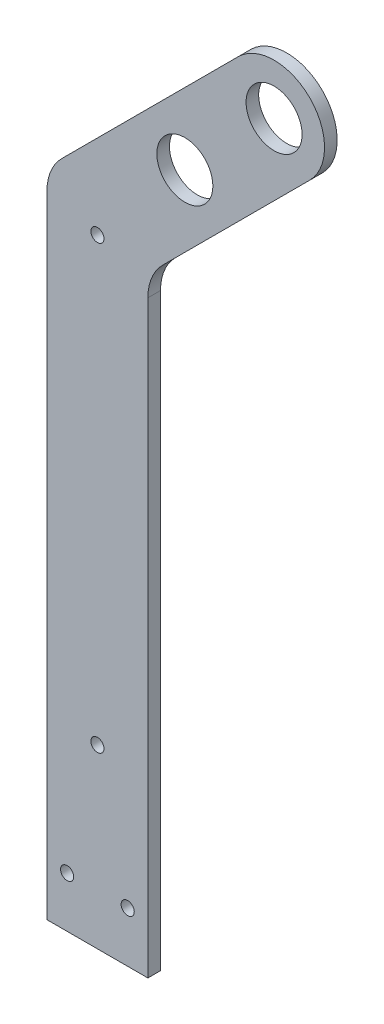
SolidWorks part; units mm, degrees
material "6061 合金"
ref_plane "前视基准面" through (0, 0, 0) normal (0, 0, 1) x (1, 0, 0)
ref_plane "上视基准面" through (0, 0, 0) normal (0, 1, 0) x (1, 0, 0)
ref_plane "右视基准面" through (0, 0, 0) normal (1, 0, 0) x (0, 0, -1)
other "Configuration Table"
sketch "草图1" plane through (0, 0, 0) normal (0, 0, 1) x (1, 0, 0)
  circle A0 centre (0, 0) radius 20
  circle A1 centre (0, 0) radius 11.1
  dimension "D1" = 40
  dimension "D2" = 22.2
extrude "凸台-拉伸1" add sketch "草图1" along normal blind 60 contours A1 | A0 region at (0, 0, 0)
ref_plane "基准面1" through (0, 0, 30) normal (0, 0, 1) x (1, 0, 0)
sketch "草图2" plane through (0, 0, 30) normal (0, 0, 1) x (1, 0, 0)
  line L0 (0, 0) -> (-70, -70) construction
  line L1 (-70, -70) -> (-70, -320) construction
  line L2 (0, -57.3148) -> (0, 49.9409) construction
  line L3 (-56.8582, 0) -> (46.4003, 0) construction
  line L4 (-14.1421, 14.1421) -> (-90, -61.7157)
  line L5 (14.1421, -14.1421) -> (-50, -78.2843)
  line L6 (-90, -61.7157) -> (-90, -320)
  line L7 (-50, -78.2843) -> (-50, -320)
  line L8 (-90, -320) -> (-50, -320)
  circle A2 centre (0, 0) radius 20 construction
  arc A3 (-14.1421, 14.1421) -> (14.1421, -14.1421) centre (0, 0) ccw
  dimension "D1" = 45
  dimension "D2" = 250
  dimension "D3" = 70
  dimension "D4" = 40
  dimension "D5" = 40
extrude "凸台-拉伸2" add sketch "草图2" along normal mid plane 60 contours L7 L8 L6 L4 A3 L5
sketch "草图4" plane through (0, 0, 60) normal (0, 0, 1) x (1, 0, 0)
  line L0 (-90, -61.7157) -> (-90, -320) construction
  line L1 (-90, -290) -> (-50, -290)
  line L2 (-90, -290) -> (-90, -350)
  line L4 (-50, -290) -> (-50, -350)
  line L5 (-50, -78.2843) -> (-50, -320) construction
  line L6 (-90, -320) -> (-50, -320) construction
  arc A0 (-90, -350) -> (-50, -350) centre (-70, -350) ccw
  circle A1 centre (-70, -350) radius 11
  dimension "D3" = 22
  dimension "D1" = 30
  dimension "D2" = 30
extrude "凸台-拉伸3" add sketch "草图4" along normal blind 5
mirror "镜向1" about plane through (0, 0, 30) normal (0, 0, 1) of "凸台-拉伸3"
sketch "草图5" plane through (0, 0, 0) normal (0, 1, 0) x (1, 0, 0)
  line L0 (0, 0) -> (0, -78.0582) construction
ref_plane "基准面2" through (-70, 0, 0) normal (-1, 0, 0) x (0, 0, 1)
sketch "草图7" plane through (-70, 0, 0) normal (-1, 0, 0) x (0, 0, 1)
  line L0 (-34.1239, -350) -> (109.535, -350) construction
sketch "草图8" plane through (0, 0, 60) normal (0, 0, 1) x (1, 0, 0)
  line L0 (0, 0) -> (-70, -70) construction
  circle A0 centre (-35.3553, -35.3553) radius 11.1
  dimension "D1" = 22.2
  dimension "D2" = 50
extrude "切除-拉伸1" cut sketch "草图8" against normal blind 100
fillet "圆角4" radius 20 2 edges at (-90, -61.7157, 30) (-50, -78.2843, 30)
fillet "圆角1" [suppressed] radius 50
fillet "圆角2" [suppressed] radius 3
sketch "草图9" plane through (0, 0, 65) normal (0, 0, 1) x (1, 0, 0)
  circle A0 centre (-70, -350) radius 13
  dimension "D1" = 26
extrude "切除-拉伸2" [suppressed] cut sketch "草图9" against normal blind 0.75
sketch "草图10" plane through (0, 0, -5) normal (0, 0, -1) x (-1, 0, 0)
  circle A0 centre (70, -350) radius 13
  dimension "D1" = 26
extrude "切除-拉伸3" [suppressed] cut sketch "草图10" against normal blind 0.75 contours A0
sketch "草图11" plane through (-90, 0, 0) normal (-1, 0, 0) x (0, 0, 1)
  circle A0 centre (48.5, -118.9949) radius 2.75
  circle A1 centre (48.5, -183.9949) radius 2.75
  circle A2 centre (48.5, -248.9949) radius 2.75
  circle A3 centre (11.5, -248.9949) radius 2.75
  circle A4 centre (11.5, -183.9949) radius 2.75
  circle A5 centre (11.5, -118.9949) radius 2.75
  dimension "D1" = 5.5
extrude "切除-拉伸4" [suppressed] cut sketch "草图11" against normal through all contours A1 | A2 | A0 | A3 | A4 | A5
sketch "草图12" [suppressed] plane through (-90, 0, 0) normal (-1, 0, 0) x (0, 0, 1)
  line L0 (30, -62.0134) -> (30, -339.6946) construction
  line L1 (10, -128.9949) -> (50, -128.9949)
  line L2 (10, -128.9949) -> (10, -173.9949)
  line L3 (10, -173.9949) -> (50, -173.9949)
  line L4 (50, -128.9949) -> (50, -173.9949)
  line L5 (10, -193.9949) -> (50, -193.9949)
  line L6 (10, -193.9949) -> (10, -238.9949)
  line L7 (10, -238.9949) -> (50, -238.9949)
  line L8 (50, -193.9949) -> (50, -238.9949)
  line L9 (10, -258.9949) -> (50, -258.9949)
  line L10 (10, -258.9949) -> (10, -290)
  line L11 (10, -290) -> (50, -290)
  line L12 (50, -258.9949) -> (50, -290)
  line L13 (19.5, -173.9949) -> (40.5, -173.9949)
  line L14 (19.5, -173.9949) -> (19.5, -193.9949)
  line L15 (19.5, -193.9949) -> (40.5, -193.9949)
  line L16 (40.5, -173.9949) -> (40.5, -193.9949)
  line L17 (19.5, -238.9949) -> (40.5, -238.9949)
  line L18 (19.5, -238.9949) -> (19.5, -258.9949)
  line L19 (19.5, -258.9949) -> (40.5, -258.9949)
  line L20 (40.5, -238.9949) -> (40.5, -258.9949)
  line L21 (60, -82.4264) -> (60, -290) construction
  line L22 (0, -290) -> (0, -82.4264) construction
  line L23 (57, -320) -> (3, -320) construction
  circle A0 centre (48.5, -118.9949) radius 2.75 construction
  circle A1 centre (48.5, -183.9949) radius 2.75 construction
  circle A2 centre (48.5, -248.9949) radius 2.75 construction
  dimension "D1" = 10
  dimension "D2" = 10
  dimension "D3" = 10
  dimension "D4" = 8
  dimension "D5" = 10
  dimension "D6" = 10
  dimension "D7" = 10
  dimension "D8" = 30
extrude "减重" [suppressed] cut sketch "草图12" against normal through all contours L0 L1 L2 L3 | L15 L0 L17 L7 L8 L5 | L0 L5 L6 L7 | L19 L0 L11 L12 L9 | L0 L9 L10 L11 | L1 L0 L13 L3 L4
fillet "圆角3" [suppressed] radius 3
sketch "草图13" plane through (0, 0, 60) normal (0, 0, 1) x (1, 0, 0)
  circle A0 centre (0, 0) radius 13
  circle A1 centre (-35.3553, -35.3553) radius 13
  dimension "D1" = 26
  dimension "D2" = 26
extrude "切除-拉伸6" [suppressed] cut sketch "草图13" against normal blind 1.75
sketch "草图14" plane through (0, 0, 0) normal (0, 0, -1) x (-1, 0, 0)
  circle A0 centre (0, 0) radius 13
  circle A1 centre (35.3553, -35.3553) radius 13
  dimension "D1" = 26
  dimension "D2" = 26
extrude "切除-拉伸7" [suppressed] cut sketch "草图14" against normal blind 1.75
sketch "草图15" [suppressed] plane through (0, 0, 0) normal (0, 0, -1) x (-1, 0, 0)
  line L0 (0, 0) -> (70, -350) construction
  line L1 (56.2719, -67.2005) -> (60.1942, -86.8121) construction
  line L2 (70, -350) -> (204.3541, -323.1292) construction
  circle A0 centre (56.2719, -67.2005) radius 2.75
  circle A1 centre (75.2172, -73.6095) radius 2.75
  circle A2 centre (60.1942, -86.8121) radius 2.75
  dimension "D1" = 5.5
  dimension "D2" = 20
  dimension "D3" = 20
  dimension "D4" = 20
  dimension "D5" = 42
  dimension "D6" = 270
extrude "切除-拉伸8" [suppressed] cut sketch "草图15" against normal through all contours A2 | A0 | A1
ref_plane "小腿主干连杆面" through (0, 0, 0) normal (0.9806, -0.1961, 0) x (0, 0, -1)
ref_plane "小腿主干对称面" through (0, 0, 30) normal (0, 0, -1) x (-1, 0, 0)
sketch "草图16" plane through (0, 0, 60) normal (0, 0, 1) x (1, 0, 0)
  line L0 (0, 0) -> (-70, -350)
  line L1 (-35.3553, -35.3553) -> (0, 0)
sketch "草图17" plane through (0, 0, 60) normal (0, 0, 1) x (1, 0, 0)
  line L0 (0, 0) -> (-70, -350) construction
  line L1 (118.6974, 32.5948) -> (32.9122, -396.3312) construction
  line L2 (92.7764, -97.0102) -> (20.2919, -82.5133)
  line L3 (73.1648, -195.0683) -> (0.6803, -180.5713)
  circle A0 centre (20.2919, -82.5133) radius 46
  circle A1 centre (0.6803, -180.5713) radius 46
  dimension "D3" = 92
  dimension "D4" = 92
  dimension "D1" = 110
  dimension "D2" = 73.92
  dimension "D5" = 180
  dimension "D6" = 280
sketch "草图18" plane through (0, 0, 60) normal (0, 0, 1) x (1, 0, 0)
  line L1 (14.1421, -14.1421) -> (-44.1421, -72.4264) construction
  line L3 (14.1421, -14.1421) -> (-44.1421, -72.4264)
  line L4 (15.4873, -12.6548) -> (52.8188, -49.9864)
  line L5 (-50, -128.5133) -> (20.2919, -128.5133)
  line L10 (-90, -290) -> (-50, -290)
  line L11 (-50, -290) -> (-50, -86.5685)
  line L12 (-44.1421, -72.4264) -> (14.1421, -14.1421)
  line L13 (-14.1421, 14.1421) -> (-84.1421, -55.8579)
  line L14 (-90, -70) -> (-90, -290)
  line L16 (-50, -128.5133) -> (-50, -86.5685)
  line L17 (-44.1421, -72.4264) -> (14.1421, -14.1421)
  circle A0 centre (20.2919, -82.5133) radius 46 construction
  arc A1 (14.1421, -14.1421) -> (-14.1421, 14.1421) centre (0, 0) ccw construction
  arc A2 (14.1421, -14.1421) -> (-14.1421, 14.1421) centre (0, 0) ccw
  arc A3 (14.1421, -14.1421) -> (15.4873, -12.6548) centre (0, 0) ccw
  arc A4 (20.2919, -128.5133) -> (52.8188, -49.9864) centre (20.2919, -82.5133) ccw
  circle A5 centre (20.2919, -82.5133) radius 35
  arc A9 (-84.1421, -55.8579) -> (-90, -70) centre (-70, -70) ccw
  arc A10 (-84.1421, -55.8579) -> (-90, -70) centre (-70, -70) ccw
  arc A11 (-44.1421, -72.4264) -> (-50, -86.5685) centre (-30, -86.5685) ccw
  arc A12 (-44.1421, -72.4264) -> (-50, -86.5685) centre (-30, -86.5685) ccw
  line M14 (-50, -290) -> (-50, -86.5685)
  line M15 (-44.1421, -72.4264) -> (14.1421, -14.1421)
  arc M16 (14.1421, -14.1421) -> (-14.1421, 14.1421) centre (0, 0) ccw
  arc M22 (-50, -86.5685) -> (-44.1421, -72.4264) centre (-30, -86.5685) cw
  dimension "D2" = 70
  dimension "D1" = 0
extrude "凸台-拉伸4" add sketch "草图18" against normal blind 5 from offset 25 contours L5 A4 L4 A5 M16 M15 M22 M14 region at (16.0508, -14.5165, 60) offset against normal yes
sketch "草图19" plane through (0, 0, 0) normal (0, 0, -1) x (-1, 0, 0)
  line L0 (50, -86.5685) -> (50, -290) construction
  line L1 (50, -134.5713) -> (50, -226.5713)
  line L2 (-0.6803, -134.5713) -> (50, -134.5713)
  line L3 (-0.6803, -226.5713) -> (50, -226.5713)
  circle A0 centre (-0.6803, -180.5713) radius 46 construction
  arc A1 (-0.6803, -134.5713) -> (-0.6803, -226.5713) centre (-0.6803, -180.5713) ccw
  circle A2 centre (-0.6803, -180.5713) radius 35
  dimension "D1" = 70
extrude "凸台-拉伸5" add sketch "草图19" against normal blind 5 from offset 25 offset against normal yes
fillet "圆角5" radius 10 2 edges at (-50, -226.5713, 27.5) (-50, -128.5133, 32.5)
sketch "草图21" plane through (0, 0, 65) normal (0, 0, 1) x (1, 0, 0)
  line L0 (-70, -350) -> (-70, -6.9331) construction
  circle A0 centre (-70, -75) radius 2.6
  circle A1 centre (-70, -250) radius 2.6
  circle A2 centre (-58, -300) radius 2.6
  circle A3 centre (-82, -300) radius 2.6
  dimension "D1" = 5.2
  dimension "D2" = 12
  dimension "D3" = 50
  dimension "D4" = 100
  dimension "D5" = 175
extrude "切除-拉伸9" cut sketch "草图21" against normal through all both and the other way through all
sketch "草图22" plane through (-90, 0, 0) normal (-1, 0, 0) x (0, 0, 1)
  line L0 (-5, -350) -> (-5, -370) construction
  line L5 (-5, -381.0864) -> (10, -381.0864)
  line L6 (-5, -381.0864) -> (-5, 64.9179)
  line L7 (-5, 64.9179) -> (10, 64.9179)
  line L8 (10, -381.0864) -> (10, 64.9179)
  line L10 (65, -370) -> (15, -370)
  line L11 (65, -370) -> (65, 61.088)
  line L12 (65, 61.088) -> (15, 61.088)
  line L13 (15, -370) -> (15, 61.088)
  dimension "D1" = 50
  dimension "D2" = 5
extrude "切除-拉伸10" cut sketch "草图22" against normal through all both contours L8 L7 L6 L5 | L13 L12 L11 L10
